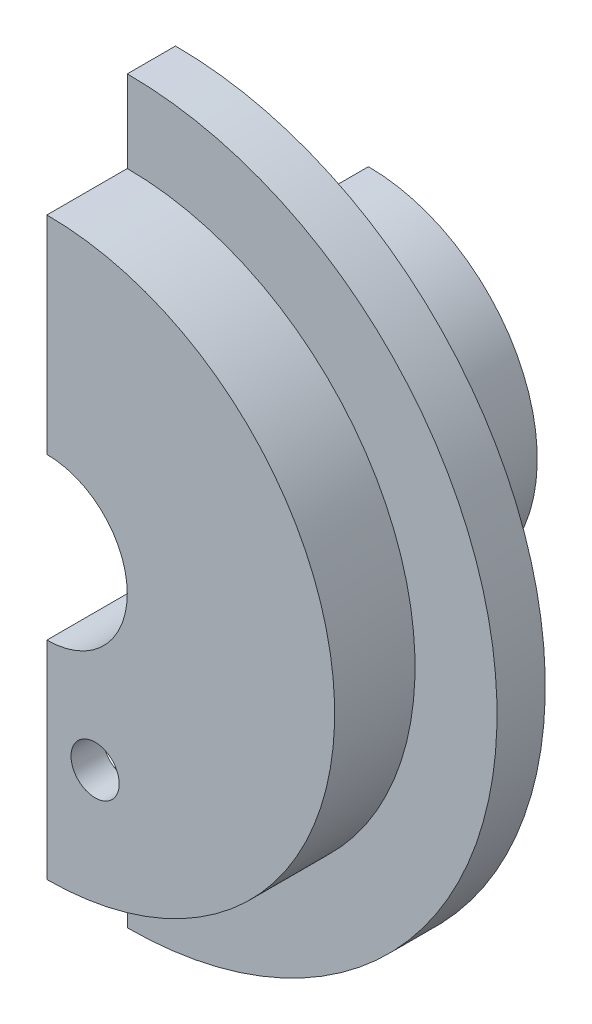
SolidWorks part; units mm, degrees
ref_plane "Front Plane" through (0, 0, 0) normal (0, 0, 1) x (1, 0, 0)
ref_plane "Top Plane" through (0, 0, 0) normal (0, 1, 0) x (1, 0, 0)
ref_plane "Right Plane" through (0, 0, 0) normal (1, 0, 0) x (0, 0, -1)
sketch "Sketch1" plane through (0, 0, 0) normal (0, 0, 1) x (1, 0, 0)
  circle A0 centre (0, 0) radius 23
  circle A1 centre (0, 0) radius 5
  dimension "D1" = 46
  dimension "D2" = 10
extrude "Boss-Extrude1" add sketch "Sketch1" along normal blind 3
sketch "Sketch2" plane through (0, 0, 3) normal (0, 0, 1) x (1, 0, 0)
  circle A0 centre (0, 0) radius 5
  circle A1 centre (0, 0) radius 17.9
  dimension "D1" = 35.8
  dimension "D2" = 10
extrude "Boss-Extrude2" add sketch "Sketch2" along normal blind 5
sketch "Sketch3" plane through (0, 0, 8) normal (0, 0, 1) x (1, 0, 0)
  circle A0 centre (0, 0) radius 23
  circle A1 centre (0, 0) radius 7
extrude "Boss-Extrude3" add sketch "Sketch3" along normal blind 3
sketch "Sketch4" plane through (0, 0, 0) normal (0, 0, -1) x (-1, 0, 0)
  circle A0 centre (0, 0) radius 5
  circle A1 centre (0, 0) radius 10.5
  dimension "D1" = 21
  dimension "D2" = 10
extrude "Boss-Extrude4" add sketch "Sketch4" along normal blind 12
ref_plane "Plane1" through (0, 0, -5) normal (0, 0, -1) x (-1, 0, 0)
sketch "Sketch5" plane through (0, 0, -5) normal (0, 0, -1) x (-1, 0, 0)
  circle A0 centre (0, 0) radius 10.5
  circle A1 centre (0, 0) radius 9
  dimension "D1" = 18
extrude "Cut-Extrude2" cut sketch "Sketch5" along normal mid plane 4
fillet "Fillet1" radius 1 2 edges at (-10.5, 0, -7) (-10.5, 0, -3)
sketch "Sketch6" plane through (0, 0, -12) normal (0, 0, -1) x (-1, 0, 0)
  line L1 (0, 23) -> (26.4306, 23)
  line L2 (0, 23) -> (0, -25.0726)
  line L3 (0, -25.0726) -> (26.4306, -25.0726)
  line L4 (26.4306, 23) -> (26.4306, -25.0726)
  circle A0 centre (0, 0) radius 23 construction
extrude "Cut-Extrude3" cut sketch "Sketch6" against normal blind 36
sketch "Sketch7" plane through (0, 0, 11) normal (0, 0, 1) x (1, 0, 0)
  line L1 (-26.6056, 38.3311) -> (35.3694, 38.3311)
  line L2 (-26.6056, 38.3311) -> (-26.6056, -29.1163)
  line L3 (-26.6056, -29.1163) -> (35.3694, -29.1163)
  line L4 (35.3694, 38.3311) -> (35.3694, -29.1163)
extrude "Cut-Extrude4" cut sketch "Sketch7" against normal up to vertex (3 mm away) up to point (0, 17.9, 8)
sketch "Sketch8" plane through (0, 0, 0) normal (-1, 0, 0) x (0, 0, 1)
  line L0 (8, -5) -> (-12, -5) construction
  line L1 (3, -7.6) -> (6, -7.6)
  line L2 (3, -7.6) -> (3, -13.4)
  line L3 (3, -13.4) -> (6, -13.4)
  line L4 (6, -7.6) -> (6, -13.4)
  line L5 (8, -5) -> (8, -17.9) construction
  dimension "D1" = 5.8
  dimension "D2" = 2.6
  dimension "D3" = 2
  dimension "D4" = 3
extrude "Cut-Extrude5" cut sketch "Sketch8" against normal blind 6
sketch "Sketch9" plane through (0, 0, 8) normal (0, 0, 1) x (1, 0, 0)
  line L0 (0, -5) -> (0, -17.9) construction
  circle A0 centre (3, -10.5) radius 1.5
  arc A1 (0, -5) -> (0, 5) centre (0, 0) ccw construction
  dimension "D1" = 3
  dimension "D3" = 10.5
  dimension "D2" = 3
extrude "Cut-Extrude6" cut sketch "Sketch9" against normal blind 9
fillet "Fillet2" radius 1 2 edges at (0, -7.6, 4.5) (0, -13.4, 4.5)
sketch "Sketch10" plane through (0, 0, 0) normal (0, 0, -1) x (-1, 0, 0)
  circle A0 centre (-3, -10.5) radius 3
  dimension "D1" = 6
extrude "Cut-Extrude7" cut sketch "Sketch10" along normal blind 30
